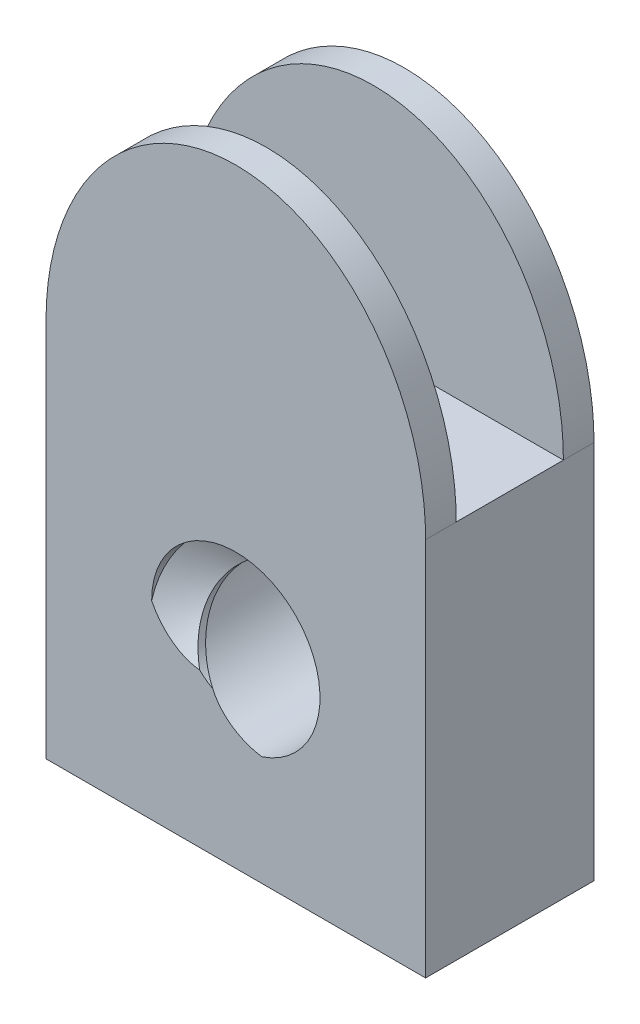
SolidWorks part; units mm, degrees
ref_plane "正面" through (0, 0, 0) normal (0, 0, 1) x (1, 0, 0)
ref_plane "平面" through (0, 0, 0) normal (0, 1, 0) x (1, 0, 0)
ref_plane "右側面" through (0, 0, 0) normal (1, 0, 0) x (0, 0, -1)
sketch "ｽｹｯﾁ1" plane through (0, 0, 0) normal (0, 0, 1) x (1, 0, 0)
  line L1 (-48.6373, 32.6643) -> (-23.8373, 32.6643)
  line L2 (-48.6373, 32.6643) -> (-48.6373, 7.8643)
  line L3 (-48.6373, 7.8643) -> (-23.8373, 7.8643)
  line L4 (-23.8373, 32.6643) -> (-23.8373, 7.8643)
  dimension "D1" = 24.8
  dimension "D2" = 24.8
extrude "ﾎﾞｽ - 押し出し1" add sketch "ｽｹｯﾁ1" along normal blind 11
sketch "ｽｹｯﾁ9" plane through (0, 32.6643, 0) normal (0, 1, 0) x (1, 0, 0)
  line L0 (-48.6373, -11) -> (-48.6373, 0) construction
  line L1 (-48.6373, -2) -> (-23.8373, -2)
  line L2 (-48.6373, -2) -> (-48.6373, -9)
  line L3 (-48.6373, -9) -> (-23.8373, -9)
  line L4 (-23.8373, -2) -> (-23.8373, -9)
  line L5 (-23.8373, -11) -> (-23.8373, 0) construction
  line L6 (-23.8373, 0) -> (-48.6373, 0) construction
  line L7 (-23.8373, -11) -> (-48.6373, -11) construction
  dimension "D1" = 7
  dimension "D2" = 24.8
  dimension "D3" = 2
  dimension "D4" = 2
sketch "ｽｹｯﾁ21" plane through (0, 0, 11) normal (0, 0, 1) x (1, 0, 0)
  line L1 (-23.8373, 7.8643) -> (-48.6373, 7.8643)
  line L2 (-23.8373, 7.8643) -> (-23.8373, 32.6643)
  line L3 (-23.8373, 32.6643) -> (-48.6373, 32.6643)
  line L4 (-48.6373, 7.8643) -> (-48.6373, 32.6643)
  dimension "D1" = 24.8
hole_wizard "M10 すきまｽﾛｯﾄ1" positions "ｽｹｯﾁ12" profile "ｽｹｯﾁ13" size "M10" standard "Ansi Metric" slot yes end condition through all
sketch "ｽｹｯﾁ12" plane through (0, 0, 0) normal (0, 0, -1) x (-1, 0, 0)
  line L0 (23.8373, 7.8643) -> (23.8373, 32.6643) construction
  line L1 (48.6373, 7.8643) -> (23.8373, 7.8643) construction
  point P0 (36.2373, 20.2643)
  point P3 (0, 0)
  dimension "D1" = 12.4
  dimension "D2" = 12.4
sketch "ｽｹｯﾁ13" plane through (-36.2373, 20.2643, 0) normal (1, 0, 0) x (0, 1, 0)
  line L0 (0, 0) -> (0, 11)
  line L1 (0, 11) -> (5.5, 11)
  line L2 (5.5, 11) -> (5.5, 0)
  line L5 (5.5, 0) -> (0, 0)
  line L11 (0, -6.35) -> (0, 107.95) construction
  dimension "通し穴の直径" = 11
  dimension "通し穴の深さ" = 11
sketch "ｽｹｯﾁ4" plane through (0, 0, 0) normal (0, 0, -1) x (-1, 0, 0)
  line L0 (23.8373, 32.6643) -> (48.6373, 32.6643) construction
  line L5 (48.6373, 7.8643) -> (48.6373, 32.6643)
  line L6 (48.6373, 32.6643) -> (23.8373, 32.6643)
  line L7 (23.8373, 32.6643) -> (23.8373, 7.8643)
  line L8 (23.8373, 7.8643) -> (48.6373, 7.8643)
  line L10 (48.6373, 32.6643) -> (23.8373, 32.6643)
  ellipse E0 centre (36.2373, 32.6643) end of major axis (36.2373, 47.6643) minor radius 12.4 (23.8373, 32.6643) -> (48.6373, 32.6643) cw
  point P1 (23.8373, 32.6643)
  point P2 (36.2373, 45.9463)
  point P7 (36.2373, 44.8211)
  point P12 (36.2373, 42.4226)
  point P15 (36.2373, 44.1584)
  dimension "D1" = 15
  dimension "D2" = 0
extrude "ﾎﾞｽ - 押し出し3" add sketch "ｽｹｯﾁ4" along direction (0, 0, 1) on the side against the normal blind 11
extrude "ｶｯﾄ - 押し出し12" cut sketch "ｽｹｯﾁ9" along normal through all
thread "ねじ山1" pitch 4 start angle 0, offset 10, length 25, pitch 10, diameter 11
ref_plane "平面5" through (-41.7373, 20.2643, 21) normal (0, 1, 0) x (1, 0, 0)
sketch "ねじ山の輪郭1" plane through (-41.7373, 20.2643, 21) normal (0, 1, 0) x (1, 0, 0)
  line L0 (0, 0) -> (0, 4) construction
  line L1 (0, 0) -> (2.1651, 1.25)
  line L2 (2.1651, 1.25) -> (2.1651, 1.75)
  line L3 (2.1651, 1.75) -> (0, 3)
  line L4 (2.1651, 1.5) -> (0, 1.5) construction
  line L11 (0, 0) -> (0, 3)
  point P2 (0, 0)
  dimension "Pitch" = 4
  dimension "Profile_Angle" = 60
  dimension "Profile_Land" = 0.5
  dimension "Profile_Height" = 2.1651
extrude "ｶｯﾄ - 押し出し14" cut sketch "ｽｹｯﾁ21" along normal through all
sketch "ｽｹｯﾁ22" plane through (0, 0, 0) normal (0, 0, -1) x (-1, 0, 0)
  line L1 (23.8373, 7.8643) -> (48.6373, 7.8643)
  line L2 (23.8373, 7.8643) -> (23.8373, 32.6643)
  line L3 (23.8373, 32.6643) -> (48.6373, 32.6643)
  line L4 (48.6373, 7.8643) -> (48.6373, 32.6643)
  dimension "D1" = 24.8
extrude "ｶｯﾄ - 押し出し15" cut sketch "ｽｹｯﾁ22" along normal through all
